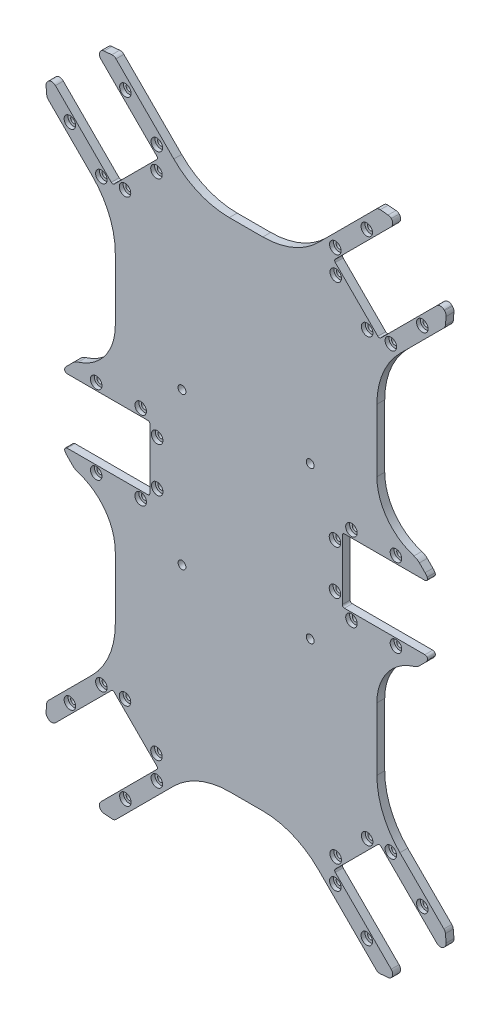
SolidWorks part; units mm, degrees
material "ABS"
ref_plane "Front Plane" through (0, 0, 0) normal (0, 0, 1) x (1, 0, 0)
ref_plane "Top Plane" through (0, 0, 0) normal (0, 1, 0) x (1, 0, 0)
ref_plane "Right Plane" through (0, 0, 0) normal (1, 0, 0) x (0, 0, -1)
sketch "Sketch1" plane through (0, 0, 0) normal (0, 0, 1) x (1, 0, 0)
  line L1 (0, 0) -> (-50, 0)
  line L2 (0, 0) -> (0, 95)
  line L3 (0, 95) -> (-50, 95)
  line L4 (-50, 0) -> (-50, 95)
  dimension "D1" = 95
  dimension "D2" = 50
sketch "Sketch2" plane through (0, 0, 0) normal (0, 0, 1) x (1, 0, 0)
  line L0 (-85.6588, 109.4959) -> (-51.3641, 75.2012)
  line L1 (-85.6588, 109.4959) -> (-59.4959, 135.6588)
  line L2 (-51.3641, 75.2012) -> (-25.2012, 101.3641)
  line L3 (-59.4959, 135.6588) -> (-25.2012, 101.3641)
  line L4 (-85.6588, 109.4959) -> (-25.2012, 101.3641) construction
  line L5 (-51.3641, 75.2012) -> (-59.4959, 135.6588) construction
  line L6 (0, 95) -> (-50, 95) construction
  line L7 (0, 0) -> (0, 95) construction
  line L8 (-52.4955, 128.6585) -> (-78.6585, 102.4955) construction
  point P1 (-55.43, 105.43)
  dimension "D1" = 135
  dimension "D2" = 37
  dimension "D3" = 48.5
  dimension "D4" = 55.43
  dimension "D5" = 10.43
  dimension "D6" = 38.6
sketch "Sketch4" plane through (0, 0, 0) normal (0, 0, 1) x (1, 0, 0)
  line L0 (-77.315, 109.9201) -> (-50.9399, 83.545)
  line L1 (-77.315, 109.9201) -> (-59.9201, 127.315)
  line L2 (-50.9399, 83.545) -> (-33.545, 100.9399)
  line L3 (-59.9201, 127.315) -> (-33.545, 100.9399)
  line L4 (-77.315, 109.9201) -> (-33.545, 100.9399) construction
  line L5 (-50.9399, 83.545) -> (-59.9201, 127.315) construction
  line L7 (-51.3641, 75.2012) -> (-25.2012, 101.3641) construction
  point P1 (-55.43, 105.43)
  dimension "D1" = 24.6
  dimension "D2" = 5.6
sketch "Sketch6" plane through (0, 0, 0) normal (0, 0, 1) x (1, 0, 0)
  line L0 (-70.5267, 101.4348) -> (-37.8409, 68.749) construction
  line L1 (-77.315, 109.9201) -> (-50.9399, 83.545) construction
  line L2 (-52.4955, 128.6585) -> (-78.6585, 102.4955) construction
  line L3 (-55.43, 105.43) -> (-38.2827, 88.2827) construction
  line L4 (-51.3641, 75.2012) -> (-25.2012, 101.3641) construction
  line L5 (-51.4348, 120.5267) -> (-18.749, 87.8409) construction
  point P0 (-70.5267, 101.4348)
  point P1 (-64.8699, 95.778)
  point P2 (-59.213, 90.1211)
  point P3 (-53.5562, 84.4643)
  point P4 (-45.778, 84.4643)
  point P16 (-34.4643, 95.778)
  point P17 (-34.4643, 103.5562)
  point P18 (-40.1211, 109.213)
  point P21 (-45.778, 114.8699)
  dimension "D1" = 6.5
  dimension "D2" = 8
  dimension "D3" = 8
  dimension "D4" = 8
  dimension "D5" = 13.5
  dimension "D6" = 8
  dimension "D7" = 36
sketch "Sketch9" plane through (0, 0, 0) normal (0, 0, 1) x (1, 0, 0)
  line L0 (-55.43, 105.43) -> (-38.2827, 88.2827) construction
  line L1 (-61.8582, 90.645) -> (-39.5695, 68.3563) construction
  line L2 (-77.315, 109.9201) -> (-50.9399, 83.545) construction
  line L3 (-52.4955, 128.6585) -> (-78.6585, 102.4955) construction
  line L4 (-40.645, 111.8582) -> (-18.3563, 89.5695) construction
  point P8 (-67.3447, 96.1315)
  point P9 (-55.3239, 84.1107)
  point P10 (-46.273, 84.2522)
  point P13 (-34.2522, 96.273)
  point P14 (-34.1107, 105.3239)
  point P15 (-46.1315, 117.3447)
  dimension "D1" = 15
  dimension "D2" = 12.5
  dimension "D3" = 17
  dimension "D4" = 8.5
  dimension "D5" = 35.8
sketch "Sketch15" plane through (0, 0, 0) normal (0, 0, 1) x (1, 0, 0)
  line L0 (-51.3641, 75.2012) -> (-25.2012, 101.3641) construction
  line L1 (-31.18, -18.5) -> (-79.68, -18.5)
  line L2 (-31.18, -18.5) -> (-31.18, 18.5)
  line L3 (-31.18, 18.5) -> (-79.68, 18.5)
  line L4 (-79.68, -18.5) -> (-79.68, 18.5)
  line L5 (-31.18, -18.5) -> (-79.68, 18.5) construction
  line L6 (-31.18, 18.5) -> (-79.68, -18.5) construction
  line L7 (-85.6588, 109.4959) -> (-51.3641, 75.2012) construction
  line L9 (-69.78, 18.5) -> (-69.78, -18.5) construction
  line L12 (-77.315, 109.9201) -> (-50.9399, 83.545) construction
  line L13 (-36.78, -12.3) -> (-74.08, -12.3)
  line L14 (-36.78, -12.3) -> (-36.78, 12.3)
  line L15 (-36.78, 12.3) -> (-74.08, 12.3)
  line L16 (-74.08, -12.3) -> (-74.08, 12.3)
  line L17 (-36.78, -12.3) -> (-74.08, 12.3) construction
  line L18 (-36.78, 12.3) -> (-74.08, -12.3) construction
  line L19 (-50.9399, 83.545) -> (-33.545, 100.9399) construction
  point P0 (-55.43, 0)
  point P12 (-55.43, 0)
  dimension "D1" = 38.6
sketch "Sketch18" plane through (0, 0, 0) normal (0, 0, 1) x (1, 0, 0)
  line L0 (-63.4757, 15) -> (-37.4054, 15) construction
  line L1 (-69.78, 18.5) -> (-69.78, -18.5) construction
  point P2 (-57.28, 15)
  point P3 (-40.28, 15)
  point P4 (-33.98, 8.5)
  dimension "D1" = 12.5
  dimension "D2" = 17
  dimension "D3" = 15
  dimension "D4" = 8.5
  dimension "D5" = 35.8
sketch "Sketch22" [suppressed] plane through (0, 0, 0) normal (0, 0, 1) x (1, 0, 0)
  line L0 (-68.7515, 13.5) -> (-41.8085, 13.5) construction
  line L1 (-69.78, 18.5) -> (-69.78, -18.5) construction
  point P2 (-63.28, 13.5)
  point P3 (-55.28, 13.5)
  point P4 (-47.28, 13.5)
  point P5 (-39.28, 13.5)
  point P6 (-33.78, 8)
  dimension "D1" = 6.5
  dimension "D2" = 8
  dimension "D3" = 8
  dimension "D4" = 8
  dimension "D5" = 8
  dimension "D6" = 36
  dimension "D7" = 13.5
sketch "Sketch3" plane through (0, 0, 0) normal (0, 0, 1) x (1, 0, 0)
  line L0 (-52.4955, 128.6585) -> (-78.6585, 102.4955)
  line L1 (-78.6585, 102.4955) -> (-50, 73.837)
  line L2 (-50, 0) -> (-50, 95) construction
  line L3 (-50, 73.837) -> (-50, 0)
  line L4 (-50, 0) -> (0, 0)
  line L5 (0, 0) -> (0, 95)
  line L6 (-52.4955, 128.6585) -> (-18.837, 95)
  line L7 (0, 95) -> (-50, 95) construction
  line L8 (-18.837, 95) -> (0, 95)
  line L9 (-59.4959, 135.6588) -> (-25.2012, 101.3641) construction
extrude "Boss-Extrude1" add sketch "Sketch3" along normal blind 3
sketch "Sketch5" plane through (0, 0, 3) normal (0, 0, 1) x (1, 0, 0)
  line L0 (-33.545, 100.9399) -> (-50.9399, 83.545)
  line L1 (-50.9399, 83.545) -> (-77.315, 109.9201)
  line L2 (-77.315, 109.9201) -> (-59.9201, 127.315)
  line L3 (-59.9201, 127.315) -> (-33.545, 100.9399)
extrude "Cut-Extrude1" cut sketch "Sketch5" against normal through all
hole_wizard "CBORE for M2 Hex Socket Head Cap Screw2" positions "Sketch11" profile "Sketch10" counterbore size "M2" standard "ISO" end condition through all
sketch "Sketch11" plane through (0, 0, 3) normal (0, 0, 1) x (1, 0, 0)
  point P0 (-67.3447, 96.1315)
  point P3 (-55.3239, 84.1107)
  point P6 (-46.273, 84.2522)
  point P9 (-34.2522, 96.273)
  point P12 (-34.1107, 105.3239)
  point P15 (-46.1315, 117.3447)
sketch "Sketch10" plane through (-67.3447, 96.1315, 3) normal (1, 0, 0) x (0, -1, 0)
  line L0 (0, 0) -> (0, 3)
  line L1 (0, 3) -> (1.2, 3)
  line L3 (1.2, 3) -> (1.2, 1.5)
  line L4 (1.2, 1.5) -> (2.2, 1.5)
  line L5 (2.2, 1.5) -> (2.2, 0)
  line L7 (2.2, 0) -> (0, 0)
  line L11 (0, -6.35) -> (0, 107.95) construction
  dimension "Thru Hole Dia." = 2.4
  dimension "Thru Hole Depth" = 3
  dimension "C'Bore Dia." = 4.4
  dimension "C'Bore Depth" = 1.5
hole_wizard "CBORE for M2 Hex Socket Head Cap Screw3" [suppressed] positions "Sketch13" profile "Sketch12" counterbore size "M2" standard "ISO"
sketch "Sketch13" [suppressed] plane through (0, 0, 3) normal (0, 0, 1) x (1, 0, 0)
  point P0 (-70.456, 101.3641)
  point P3 (-64.7992, 95.7073)
  point P6 (-59.1423, 90.0504)
  point P9 (-53.4855, 84.3936)
  point P12 (-45.7073, 84.3936)
  point P15 (-34.3936, 95.7073)
  point P18 (-34.3936, 103.4855)
  point P21 (-40.0504, 109.1423)
  point P24 (-45.7073, 114.7992)
  point P27 (-51.3641, 120.456)
sketch "Sketch12" plane through (-70.456, 101.3641, 3) normal (1, 0, 0) x (0, -1, 0)
  line L0 (0, 0) -> (0, 3)
  line L1 (0, 3) -> (1.2, 3)
  line L3 (1.2, 3) -> (1.2, 1.5)
  line L4 (1.2, 1.5) -> (2.2, 1.5)
  line L5 (2.2, 1.5) -> (2.2, 0)
  line L7 (2.2, 0) -> (0, 0)
  line L11 (0, -6.35) -> (0, 107.95) construction
  dimension "Thru Hole Dia." = 2.4
  dimension "Thru Hole Depth" = 3
  dimension "C'Bore Dia." = 4.4
  dimension "C'Bore Depth" = 1.5
sketch "Sketch16" plane through (0, 0, 3) normal (0, 0, 1) x (1, 0, 0)
  line L0 (-50, 18.5) -> (-69.78, 18.5)
  line L1 (-31.18, 18.5) -> (-79.68, 18.5) construction
  line L2 (-50, 73.837) -> (-50, 0) construction
  line L3 (-69.78, 18.5) -> (-69.78, 12.3)
  line L4 (-36.78, 12.3) -> (-74.08, 12.3) construction
  line L5 (-69.78, 18.5) -> (-69.78, -18.5) construction
  line L6 (-69.78, 12.3) -> (-50, 12.3)
  line L7 (-50, 12.3) -> (-50, 18.5)
extrude "Boss-Extrude2" add sketch "Sketch16" against normal up to surface (3 mm away) up to face at (-66.1447, 96.1315, 0)
sketch "Sketch21" plane through (0, 0, 3) normal (0, 0, 1) x (1, 0, 0)
  line L0 (-50, 12.3) -> (-50, 0)
  line L1 (-50, 0) -> (-36.78, 0)
  line L2 (-36.78, -12.3) -> (-36.78, 12.3) construction
  line L3 (-36.78, 0) -> (-36.78, 12.3)
  line L4 (-36.78, 12.3) -> (-50, 12.3)
extrude "Cut-Extrude3" cut sketch "Sketch21" against normal up to next
sketch "Sketch14" plane through (0, 0, 3) normal (0, 0, 1) x (1, 0, 0)
  line L0 (-36.78, 0) -> (0, 0) construction
  line L1 (0, 0) -> (0, 95) construction
  circle A0 centre (-24.5, 29) radius 1.5
  dimension "D1" = 3
  dimension "D2" = 29
  dimension "D3" = 24.5
extrude "Cut-Extrude2" cut sketch "Sketch14" against normal through all
hole_wizard "CBORE for M2 Hex Socket Head Cap Screw4" positions "Sketch20" profile "Sketch19" counterbore size "M2" standard "ISO" end condition through all
sketch "Sketch20" plane through (0, 0, 3) normal (0, 0, 1) x (1, 0, 0)
  point P0 (-57.28, 15)
  point P3 (-40.28, 15)
  point P6 (-33.98, 8.5)
sketch "Sketch19" plane through (-57.28, 15, 3) normal (1, 0, 0) x (0, -1, 0)
  line L0 (0, 0) -> (0, 3)
  line L1 (0, 3) -> (1.2, 3)
  line L3 (1.2, 3) -> (1.2, 1.5)
  line L4 (1.2, 1.5) -> (2.2, 1.5)
  line L5 (2.2, 1.5) -> (2.2, 0)
  line L7 (2.2, 0) -> (0, 0)
  line L11 (0, -6.35) -> (0, 107.95) construction
  dimension "Thru Hole Dia." = 2.4
  dimension "Thru Hole Depth" = 3
  dimension "C'Bore Dia." = 4.4
  dimension "C'Bore Depth" = 1.5
hole_wizard "CBORE for M2 Hex Socket Head Cap Screw5" [suppressed] positions "Sketch24" profile "Sketch23" counterbore size "M2" standard "ISO"
sketch "Sketch24" plane through (0, 0, 3) normal (0, 0, 1) x (1, 0, 0)
  point P0 (-63.28, 13.5)
  point P3 (-55.28, 13.5)
  point P6 (-47.28, 13.5)
  point P9 (-39.28, 13.5)
  point P12 (-33.78, 8)
sketch "Sketch23" plane through (-63.28, 13.5, 3) normal (1, 0, 0) x (0, -1, 0)
  line L0 (0, 0) -> (0, 3)
  line L1 (0, 3) -> (1.2, 3)
  line L3 (1.2, 3) -> (1.2, 1.5)
  line L4 (1.2, 1.5) -> (2.2, 1.5)
  line L5 (2.2, 1.5) -> (2.2, 0)
  line L7 (2.2, 0) -> (0, 0)
  line L11 (0, -6.35) -> (0, 107.95) construction
  dimension "Thru Hole Dia." = 2.4
  dimension "Thru Hole Depth" = 3
  dimension "C'Bore Dia." = 4.4
  dimension "C'Bore Depth" = 1.5
fillet "Fillet1" radius 30 2 edges at (-50, 73.837, 1.5) (-18.837, 95, 1.5)
chamfer "Chamfer1" distance 3 angle 50 2 edges at (-52.4955, 128.6585, 1.5) (-78.6585, 102.4955, 1.5) first distance on face at (-40.0597, 116.2226, 1.5) first distance on face at (-76.4664, 104.6875, 1.5)
fillet "Fillet2" radius 2 6 edges at (-76.1304, 99.9674, 1.5) (-76.5371, 104.6168, 1.5) (-55.0236, 126.1304, 1.5) (-50.3742, 126.5371, 1.5) (-74.2744, 106.8796, 1.5) (-56.8796, 124.2744, 1.5)
fillet "Fillet3" radius 0.8 2 edges at (-50.9399, 83.545, 1.5) (-33.545, 100.9399, 1.5)
chamfer "Chamfer2" distance 5 angle 45 1 edges at (-69.78, 18.5, 1.5)
fillet "Fillet5" radius 5 2 edges at (-69.78, 13.5, 1.5) (-64.78, 18.5, 1.5)
fillet "Fillet6" radius 1 1 edges at (-69.78, 12.3, 1.5)
fillet "Fillet7" [suppressed] radius 1
fillet "Fillet8" radius 0.8 1 edges at (-36.78, 12.3, 1.5)
fillet "Fillet4" radius 20 1 edges at (-50, 18.5, 1.5)
mirror "Mirror1" about plane through (0, 0, 0) normal (1, 0, 0) of bodies 110 103
mirror "Mirror2" about plane through (0, 0, 0) normal (0, 1, 0) of bodies 104
